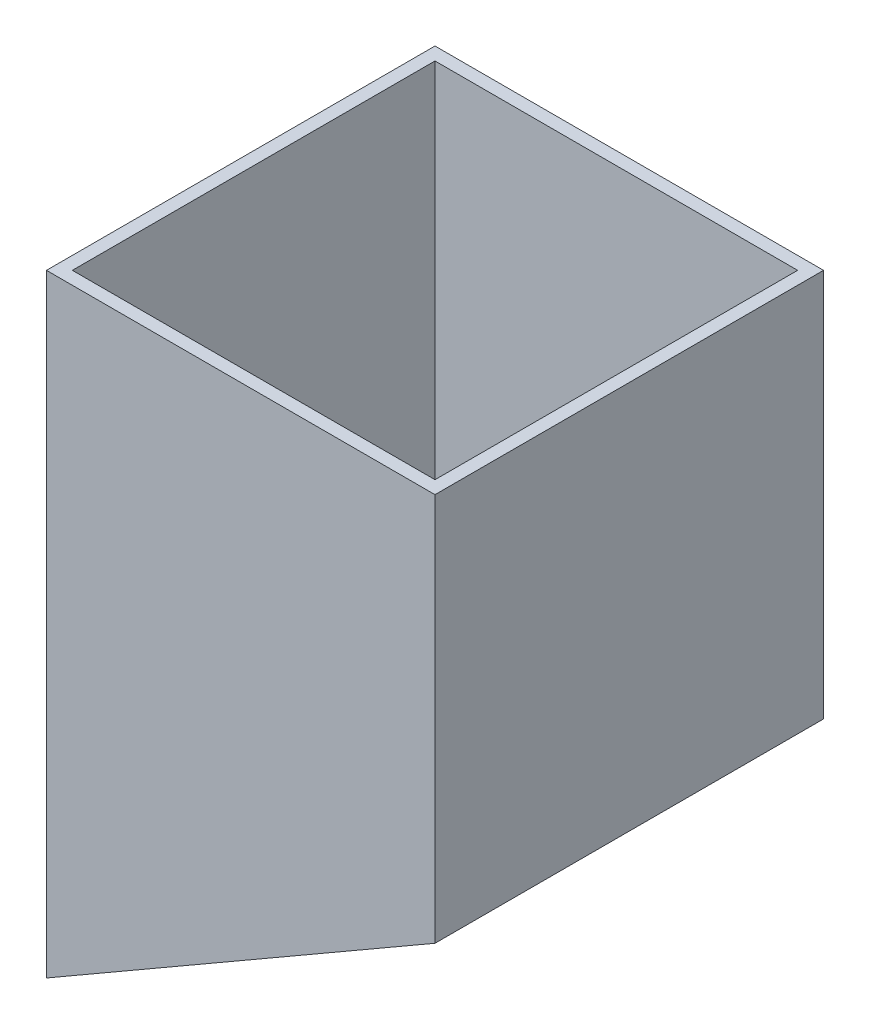
SolidWorks part; units mm, degrees
ref_plane "Alzado" through (0, 0, 0) normal (0, 0, 1) x (1, 0, 0)
ref_plane "Planta" through (0, 0, 0) normal (0, 1, 0) x (1, 0, 0)
ref_plane "Vista lateral" through (0, 0, 0) normal (1, 0, 0) x (0, 0, -1)
sketch "Croquis1" plane through (0, 0, 0) normal (0, 1, 0) x (1, 0, 0)
  line L1 (0, 0) -> (300, 0)
  line L2 (0, 0) -> (0, 300)
  line L3 (0, 300) -> (300, 300)
  line L4 (300, 0) -> (300, 300)
  dimension "D1" = 300
  dimension "D2" = 300
extrude "Saliente-Extruir1" add sketch "Croquis1" along normal blind 300
sketch "Croquis2" plane through (0, 0, 0) normal (0, 0, 1) x (1, 0, 0)
  line L0 (0, 0) -> (0, -173.2051)
  line L1 (0, -173.2051) -> (300, 0)
  line L2 (300, 0) -> (0, 0)
  dimension "D1" = 30
extrude "Saliente-Extruir2" add sketch "Croquis2" against normal up to surface (300 mm away) up to face at (150, 150, -300)
shell "Vaciado4" thickness 10 removed face at (150, 300, -150)
